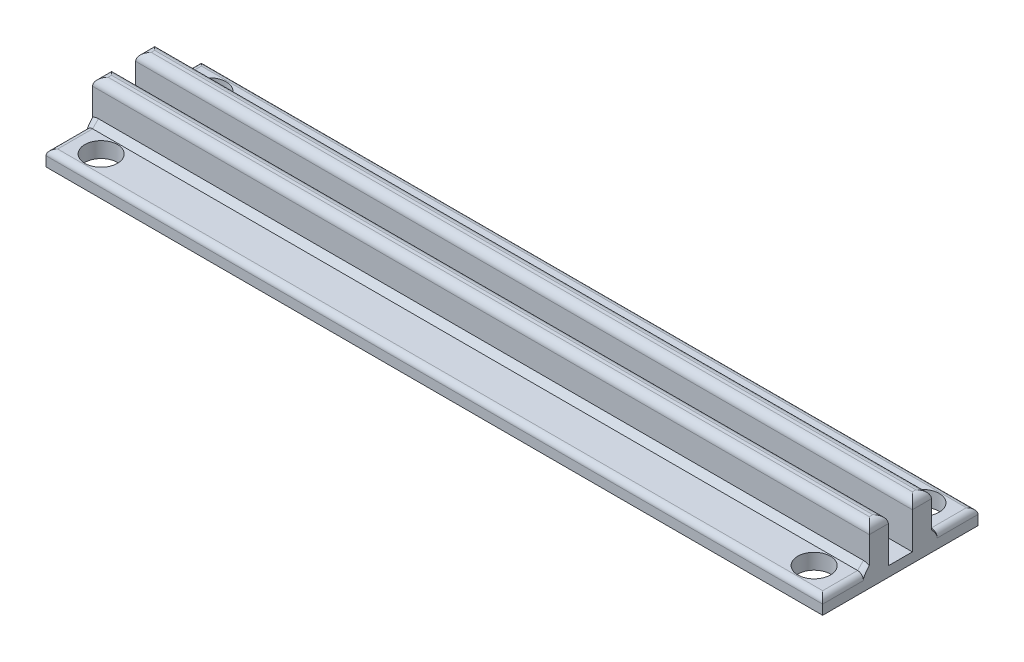
SolidWorks part; units mm, degrees
ref_plane "Front Plane" through (0, 0, 0) normal (0, 0, 1) x (1, 0, 0)
ref_plane "Top Plane" through (0, 0, 0) normal (0, 1, 0) x (1, 0, 0)
ref_plane "Right Plane" through (0, 0, 0) normal (1, 0, 0) x (0, 0, -1)
sketch "Sketch1" plane through (0, 0, 0) normal (0, 1, 0) x (1, 0, 0)
  line L1 (-50, -4) -> (50, -4)
  line L2 (-50, -4) -> (-50, 4)
  line L3 (-50, 4) -> (50, 4)
  line L4 (50, -4) -> (50, 4)
  line L5 (-50, -4) -> (50, 4) construction
  line L6 (-50, 4) -> (50, -4) construction
  point P0 (0, 0)
  dimension "D1" = 100
  dimension "D2" = 8
extrude "Boss-Extrude1" add sketch "Sketch1" along normal blind 7
sketch "Sketch3" plane through (0, 0, 0) normal (0, 1, 0) x (1, 0, 0)
  line L1 (-50, -10) -> (50, -10)
  line L2 (-50, -10) -> (-50, 10)
  line L3 (-50, 10) -> (50, 10)
  line L4 (50, -10) -> (50, 10)
  line L5 (-50, -10) -> (50, 10) construction
  line L6 (-50, 10) -> (50, -10) construction
  point P0 (0, 0)
  dimension "D1" = 100
  dimension "D2" = 20
extrude "Boss-Extrude2" add sketch "Sketch3" along normal blind 2
sketch "Sketch2" plane through (0, 7, 0) normal (0, 1, 0) x (1, 0, 0)
  line L0 (50, -4) -> (50, 4) construction
  line L1 (-50, -1.55) -> (50, -1.55)
  line L2 (-50, -1.55) -> (-50, 1.55)
  line L3 (-50, 1.55) -> (50, 1.55)
  line L4 (50, -1.55) -> (50, 1.55)
  line L5 (-50, -1.55) -> (50, 1.55) construction
  line L6 (-50, 1.55) -> (50, -1.55) construction
  point P0 (0, 0)
  dimension "D1" = 3.1
extrude "Cut-Extrude1" cut sketch "Sketch2" against normal blind 5.7
fillet "Fillet1" radius 1 8 edges at (50, 7, 2.775) (50, 7, -2.775) (-50, 7, 2.775) (-50, 7, -2.775) (0, 7, -4) (0, 7, 1.55) (0, 7, 4) (0, 7, -1.55)
sketch "Sketch4" plane through (0, 2, 0) normal (0, 1, 0) x (1, 0, 0)
  line L0 (-50, 10) -> (-50, 4) construction
  line L1 (-50, -4) -> (-50, -10) construction
  line L2 (50, 4) -> (50, 10) construction
  circle A0 centre (-45.9, 7) radius 2.1
  circle A1 centre (-45.9, -7) radius 2.1
  circle A2 centre (45.9, 7) radius 2.1
  circle A3 centre (45.9, -7) radius 2.1
  point P10 (-50, 7)
  point P13 (-50, -7)
  point P16 (0, 0)
  point P17 (0, 0)
  dimension "D1" = 4.1
  dimension "D3" = 4.2
  dimension "D4" = 4.2
  dimension "D5" = 4.2
  dimension "D6" = 4.2
  dimension "D2" = 4.1
extrude "Cut-Extrude2" cut sketch "Sketch4" against normal blind 2
fillet "Fillet2" radius 0.75 6 edges at (50, 2, -7) (50, 2, 7) (0, 2, 10) (-50, 2, 7) (-50, 2, -7) (0, 2, -10)
chamfer "Chamfer1" distance 0.75 angle 45 6 edges at (49.7803, 1.7803, 4) (-49.7803, 1.7803, 4) (0, 2, 4) (-49.7803, 1.7803, -4) (49.7803, 1.7803, -4) (0, 2, -4)
